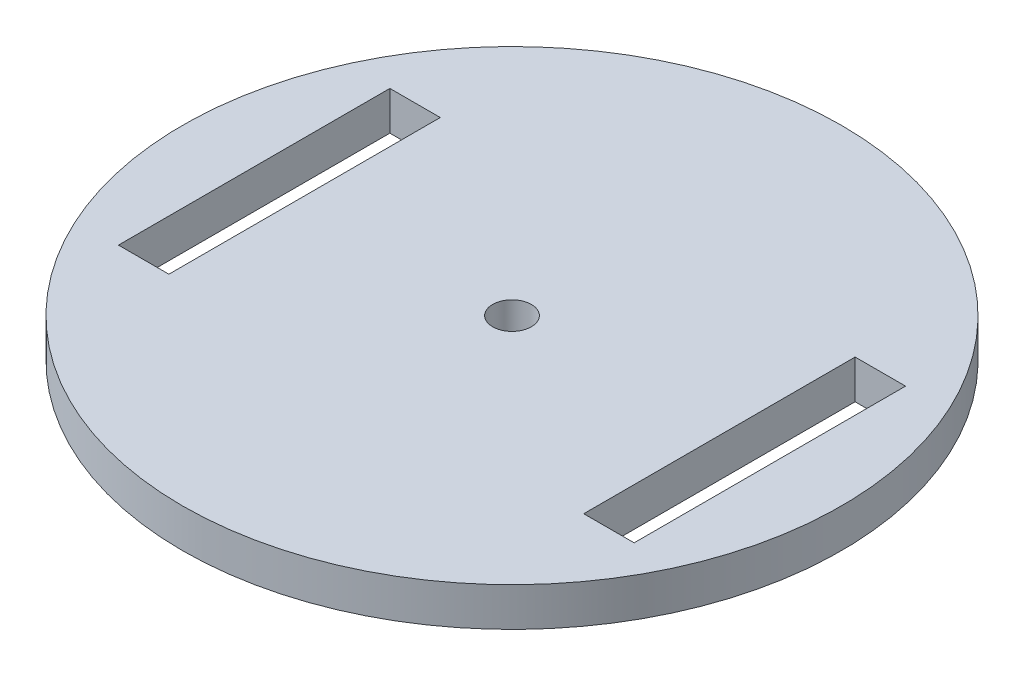
SolidWorks part; units mm, degrees
ref_plane "Front Plane" through (0, 0, 0) normal (0, 0, 1) x (1, 0, 0)
ref_plane "Top Plane" through (0, 0, 0) normal (0, 1, 0) x (1, 0, 0)
ref_plane "Right Plane" through (0, 0, 0) normal (1, 0, 0) x (0, 0, -1)
sketch "Sketch1" plane through (0, 0, 0) normal (0, 1, 0) x (1, 0, 0)
  line L0 (0, 31.7824) -> (0, -31.7824)
  line L1 (-66.5, 35) -> (-53.5, 35)
  line L2 (-66.5, 35) -> (-66.5, -35)
  line L3 (-66.5, -35) -> (-53.5, -35)
  line L4 (-53.5, 35) -> (-53.5, -35)
  line L5 (-66.5, 35) -> (-53.5, -35) construction
  line L6 (-66.5, -35) -> (-53.5, 35) construction
  line L7 (66.5, -35) -> (53.5, -35)
  line L8 (66.5, 35) -> (53.5, 35)
  line L9 (53.5, 35) -> (53.5, -35)
  line L10 (66.5, 35) -> (66.5, -35)
  circle A0 centre (0, 0) radius 85
  point P3 (-60, 0)
  point P11 (0, 0)
  dimension "D1" = 170
  dimension "D2" = 60
  dimension "D3" = 13
  dimension "D4" = 70
extrude "Boss-Extrude1" add sketch "Sketch1" along normal blind 10 contours A0 L8 L10 L7 L9 L1 L4 L3 L2 region at (-82.5958, 0, 0)
sketch "Sketch2" plane through (0, 0, 0) normal (0, -1, 0) x (1, 0, 0)
  circle A0 centre (0, 0) radius 5
  dimension "D1" = 10
extrude "Cut-Extrude1" cut sketch "Sketch2" against normal up to next
